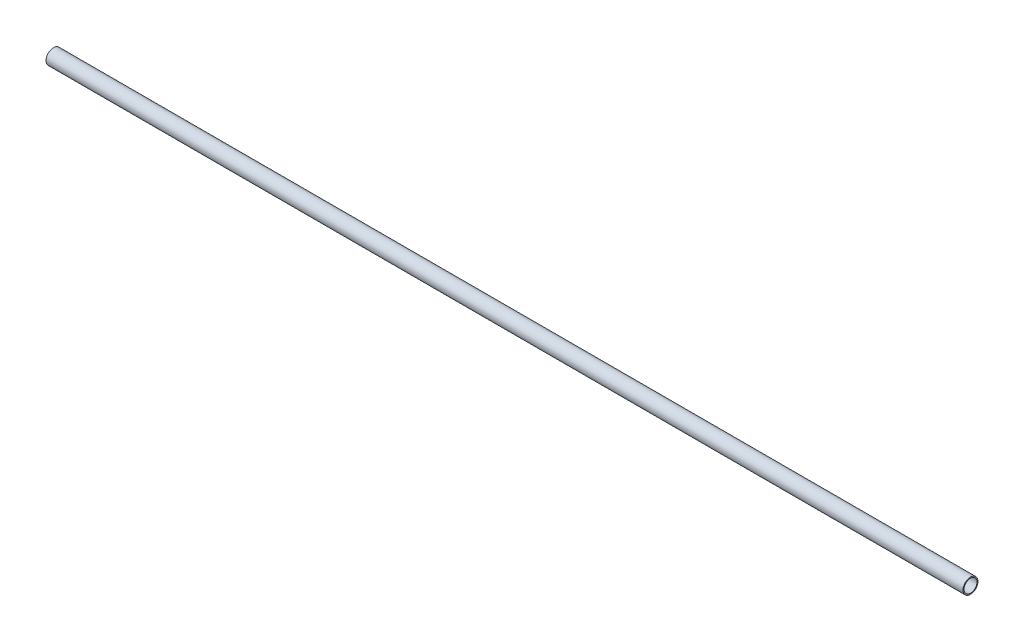
SolidWorks part; units mm, degrees
ref_plane "Front Plane" through (0, 0, 0) normal (0, 0, 1) x (1, 0, 0)
ref_plane "Top Plane" through (0, 0, 0) normal (0, 1, 0) x (1, 0, 0)
ref_plane "Right Plane" through (0, 0, 0) normal (1, 0, 0) x (0, 0, -1)
ref_axis "Axis1" through (-88.99, 0, 0) along (1, 0, 0)
sketch "Sketch1" plane through (0, 0, 0) normal (1, 0, 0) x (0, 0, -1)
  circle A0 centre (0, 0) radius 0.635
  circle A1 centre (0, 0) radius 0.7366
  dimension "D1" = 1.4732
  dimension "D2" = 1.27
extrude "Boss-Extrude1" add sketch "Sketch1" along normal blind 90
